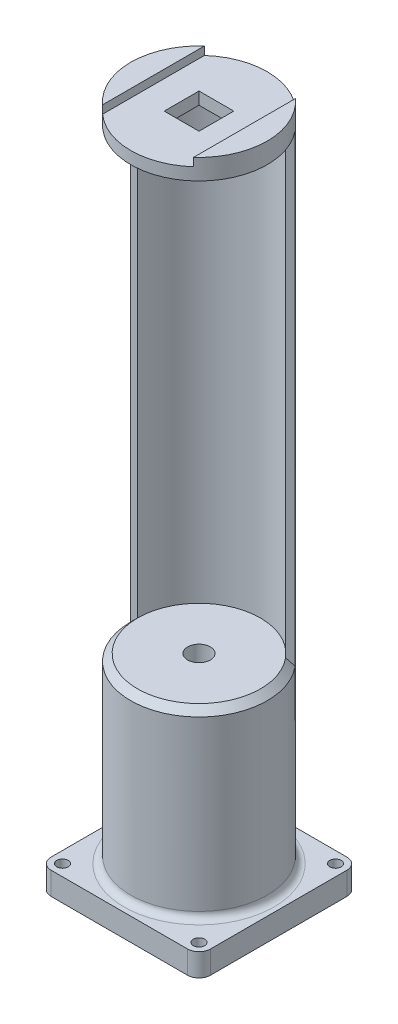
SolidWorks part; units mm, degrees
ref_plane "Front Plane" through (0, 0, 0) normal (0, 0, 1) x (1, 0, 0)
ref_plane "Top Plane" through (0, 0, 0) normal (0, 1, 0) x (1, 0, 0)
ref_plane "Right Plane" through (0, 0, 0) normal (1, 0, 0) x (0, 0, -1)
sketch "Sketch1" plane through (0, 0, 0) normal (0, 1, 0) x (1, 0, 0)
  line L1 (0, 0) -> (350, 0)
  line L2 (0, 0) -> (0, 350)
  line L3 (0, 350) -> (350, 350)
  line L4 (350, 0) -> (350, 350)
extrude "Boss-Extrude1" add sketch "Sketch1" against normal blind 50
fillet "Fillet1" radius 25 4 edges at (0, -25, -350) (350, -25, -350) (350, -25, 0) (0, -25, 0)
sketch "Sketch2" plane through (0, 0, 0) normal (0, 1, 0) x (1, 0, 0)
  circle A0 centre (25, 25) radius 12.5
  circle A1 centre (325, 25) radius 12.5
  circle A2 centre (325, 325) radius 12.5
  circle A3 centre (25, 325) radius 12.5
  dimension "D1" = 2
  dimension "D2" = 2
extrude "Cut-Extrude1" cut sketch "Sketch2" against normal blind 50
sketch "Sketch3" plane through (0, 0, 0) normal (0, 1, 0) x (1, 0, 0)
  circle A0 centre (175, 175) radius 150
extrude "Boss-Extrude2" add sketch "Sketch3" along normal blind 400
fillet "Fillet2" radius 15 1 edges at (175, 0, -325)
chamfer "Chamfer1" distance 15 angle 45 1 edges at (175, 400, -25)
sketch "Sketch4" plane through (0, 400, 0) normal (0, 1, 0) x (1, 0, 0)
  circle A0 centre (175, 175) radius 25
extrude "Cut-Extrude2" cut sketch "Sketch4" against normal through all
sketch "Sketch5" plane through (0, -50, 0) normal (0, -1, 0) x (1, 0, 0)
  line L1 (265, -85) -> (85, -85)
  line L2 (265, -85) -> (265, -265)
  line L3 (265, -265) -> (85, -265)
  line L4 (85, -85) -> (85, -265)
  line L5 (265, -85) -> (85, -265) construction
  line L6 (265, -265) -> (85, -85) construction
  point P0 (175, -175)
extrude "Cut-Extrude3" cut sketch "Sketch5" against normal blind 165
scale "Scale1" scale about origin uniform scaling yes scale factor 0.333333
sketch "Sketch6" plane through (0, 133.3333, 0) normal (0, 1, 0) x (1, 0, 0)
  arc A0 (8.3333, 58.3333) -> (96.6356, 90.4727) centre (58.3333, 58.3333) cw
  circle A1 centre (58.3333, 58.3333) radius 50 construction
  circle A2 centre (58.3333, 58.3333) radius 50 construction
extrude "Extrude-Thin1" add sketch "Sketch6" against normal blind 5 and the other way blind 350 thin thin type one direction wall 5
sketch "Sketch7" plane through (0, 483.3333, 0) normal (0, 1, 0) x (1, 0, 0)
  circle A0 centre (58.3333, 58.3333) radius 50
extrude "Boss-Extrude3" add sketch "Sketch7" against normal blind 15 contours A0
sketch "Sketch8" plane through (0, 468.3333, 0) normal (0, -1, 0) x (1, 0, 0)
  line L1 (45.5833, -71.0833) -> (71.0833, -71.0833)
  line L2 (45.5833, -71.0833) -> (45.5833, -45.5833)
  line L3 (45.5833, -45.5833) -> (71.0833, -45.5833)
  line L4 (71.0833, -71.0833) -> (71.0833, -45.5833)
  line L5 (45.5833, -71.0833) -> (71.0833, -45.5833) construction
  line L6 (45.5833, -45.5833) -> (71.0833, -71.0833) construction
  point P0 (58.3333, -58.3333)
extrude "Cut-Extrude4" cut sketch "Sketch8" against normal blind 9.5
sketch "Sketch9" plane through (0, 483.3333, 0) normal (0, 1, 0) x (1, 0, 0)
  line L1 (91.6667, 108.3333) -> (25, 108.3333)
  line L2 (91.6667, 108.3333) -> (91.6667, 8.3333)
  line L3 (91.6667, 8.3333) -> (25, 8.3333)
  line L4 (25, 108.3333) -> (25, 8.3333)
  line L5 (91.6667, 108.3333) -> (25, 8.3333) construction
  line L6 (91.6667, 8.3333) -> (25, 108.3333) construction
  circle A0 centre (58.3333, 58.3333) radius 50 construction
  point P0 (58.3333, 58.3333)
extrude "Cut-Extrude5" cut sketch "Sketch9" against normal blind 6
